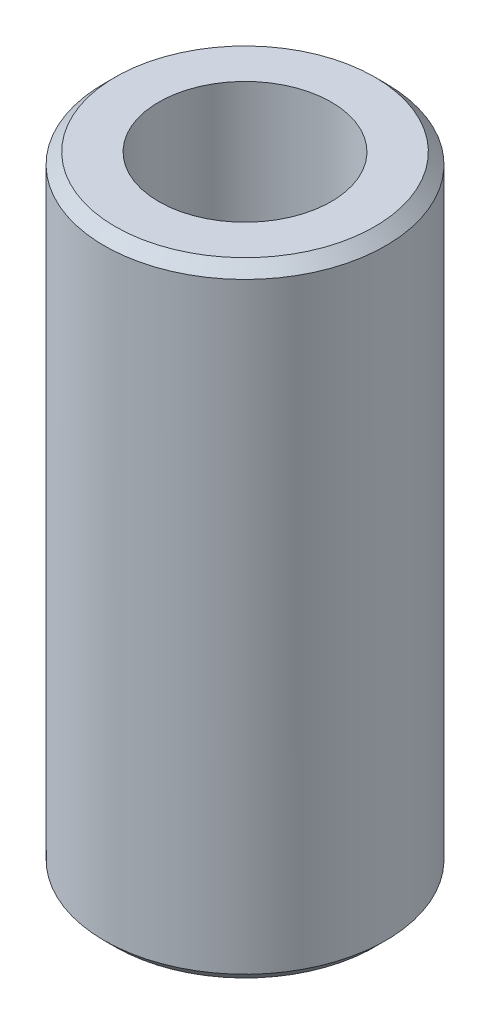
SolidWorks part; units mm, degrees
ref_plane "Front Plane" through (0, 0, 0) normal (0, 0, 1) x (1, 0, 0)
ref_plane "Top Plane" through (0, 0, 0) normal (0, 1, 0) x (1, 0, 0)
ref_plane "Right Plane" through (0, 0, 0) normal (1, 0, 0) x (0, 0, -1)
sketch "Sketch1" plane through (0, 0, 0) normal (0, 1, 0) x (1, 0, 0)
  circle A0 centre (0, 0) radius 50
  dimension "SHAFT_OD" = 100
extrude "Boss-Extrude1" add sketch "Sketch1" along normal blind 221.6816
sketch "Sketch2" plane through (0, 0, 0) normal (0, 1, 0) x (1, 0, 0)
  circle A0 centre (0, 0) radius 30.6545
  dimension "BORE_D" = 61.309
extrude "Cut-Extrude1" cut sketch "Sketch2" along normal through all
chamfer "Chamfer1" distance 3.9279 angle 45 2 edges at (0, 221.6816, 50) (0, 0, 50)
